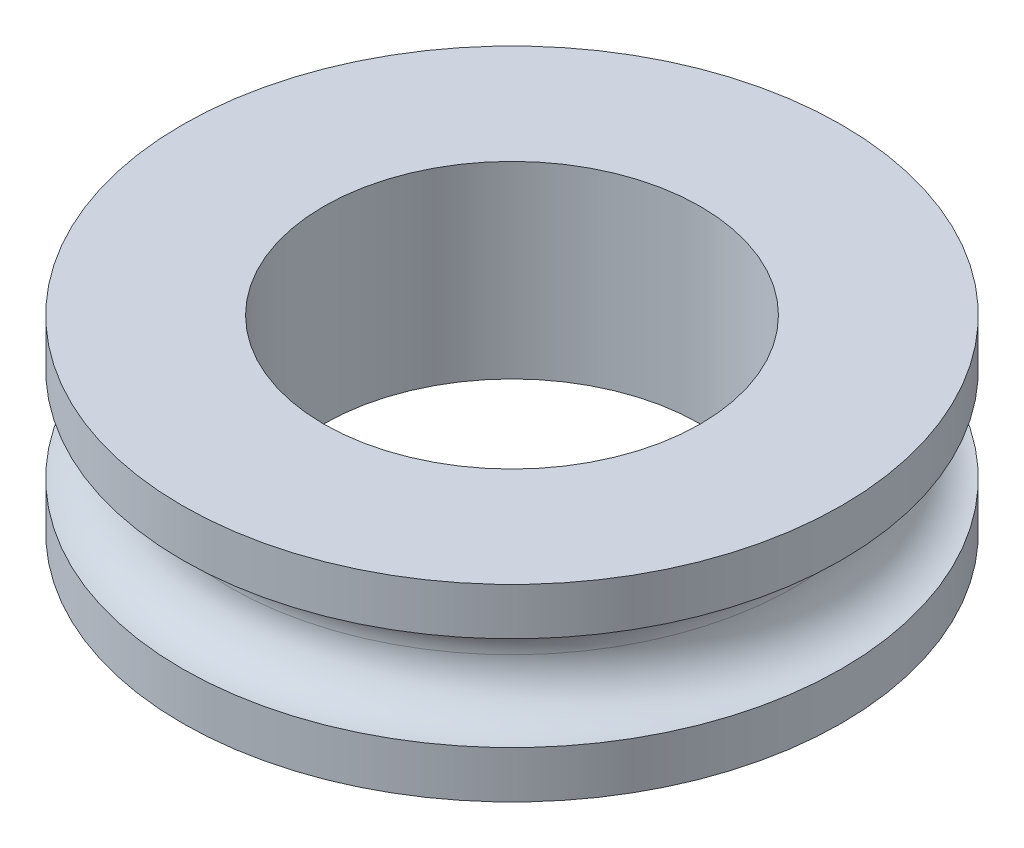
SolidWorks part; units mm, degrees
material "AISI 304"
ref_plane "前视基准面" through (0, 0, 0) normal (0, 0, 1) x (1, 0, 0)
ref_plane "上视基准面" through (0, 0, 0) normal (0, 1, 0) x (1, 0, 0)
ref_plane "右视基准面" through (0, 0, 0) normal (1, 0, 0) x (0, 0, -1)
sketch "草图1" plane through (0, 0, 0) normal (0, 1, 0) x (1, 0, 0)
  circle A0 centre (0, 0) radius 7
  circle A1 centre (0, 0) radius 6
  circle A2 centre (0, 0) radius 4
  dimension "D1" = 14
  dimension "D2" = 12
  dimension "D3" = 8
extrude "凸台-拉伸1" add sketch "草图1" along normal mid plane 4 contours A0 A1 | A1 A2 region at (-6.802, 0, 0) region at (-5.8303, 0, 0)
extrude "切除-拉伸1" cut sketch "草图1<3>" against normal mid plane 2 contours A0 A1 region at (-6.802, 0, 0)
sketch "草图1<3>" plane through (0, 0, 0) normal (0, 1, 0) x (1, 0, 0) same geometry as "草图1"
fillet "圆角1" radius 1 2 edges at (0, -1, 6) (0, 1, 6)
